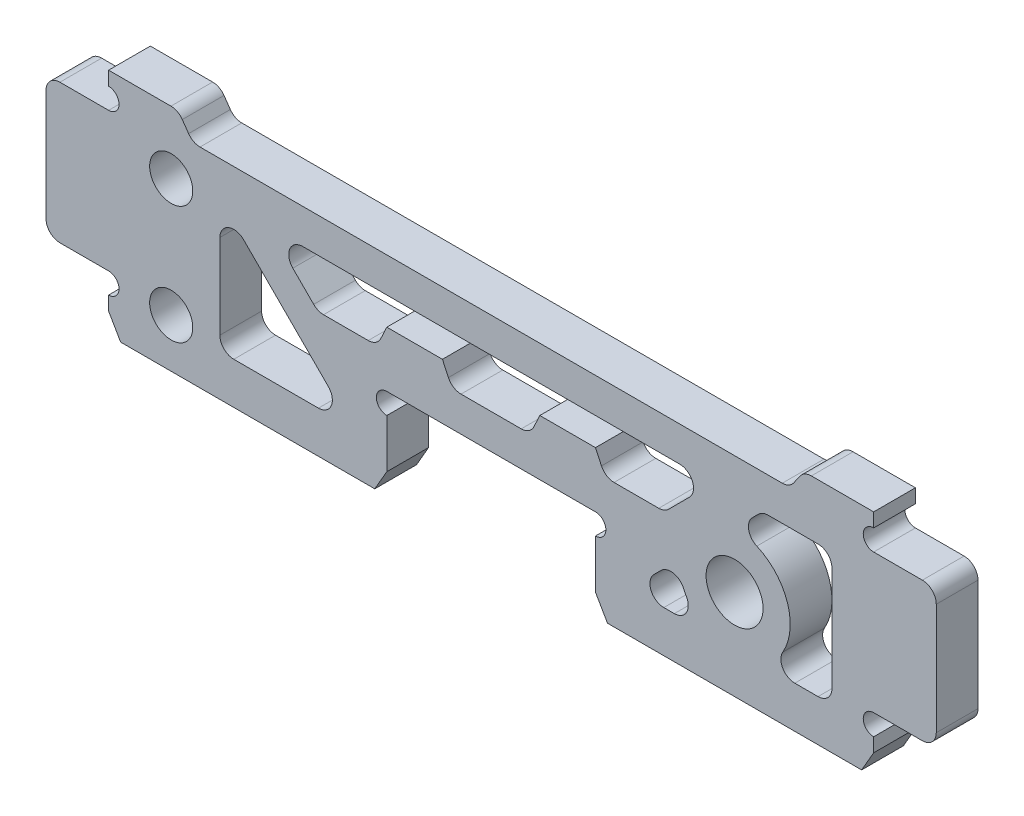
SolidWorks part; units mm, degrees
ref_plane "前视基准面" through (0, 0, 0) normal (0, 0, 1) x (1, 0, 0)
ref_plane "上视基准面" through (0, 0, 0) normal (0, 1, 0) x (1, 0, 0)
ref_plane "右视基准面" through (0, 0, 0) normal (1, 0, 0) x (0, 0, -1)
sketch "草图1" plane through (0, 0, 0) normal (0, 0, 1) x (1, 0, 0)
  line L0 (10, 10) -> (10, -5)
  line L1 (10, -5) -> (-10, -5)
  line L2 (-10, -5) -> (-10, 0)
  line L3 (-10, 0) -> (-25, 0)
  line L4 (-25, 0) -> (-25, -5)
  line L5 (-25, -5) -> (-45, -5)
  line L6 (-45, -5) -> (-45, 10)
  line L7 (-45, 10) -> (10, 10)
  circle A0 centre (0, 0) radius 2.05
  dimension "D1" = 10
  dimension "D2" = 4.1
  dimension "D3" = 5
  dimension "D4" = 5
  dimension "D5" = 20
  dimension "D6" = 15
  dimension "D7" = 55
  dimension "D8" = 15
extrude "凸台-拉伸1" add sketch "草图1" along normal mid plane 3
sketch "草图2" plane through (0, 0, 1.5) normal (0, 0, 1) x (1, 0, 0)
  line L0 (10, -2.5) -> (14.5, -2.5)
  line L1 (10, -5) -> (10, 10) construction
  line L2 (14.5, -2.5) -> (14.5, 7.5)
  line L3 (14.5, 7.5) -> (10, 7.5)
  line L4 (10, 7.5) -> (10, -2.5)
  line L5 (-45, 7.5) -> (-49.5, 7.5)
  line L6 (-45, 10) -> (-45, -5) construction
  line L7 (-49.5, 7.5) -> (-49.5, -2.5)
  line L8 (-49.5, -2.5) -> (-45, -2.5)
  line L9 (-45, -2.5) -> (-45, 7.5)
  line L10 (10, 10) -> (-45, 10) construction
  point P5 (10, 2.5)
  dimension "D1" = 10
  dimension "D2" = 4.5
  dimension "D3" = 4.5
  dimension "D4" = 2.5
extrude "凸台-拉伸2" add sketch "草图2" against normal up to surface (3 mm away) up to face at (-17.5, 0, -1.5)
sketch "草图3" plane through (0, 0, 1.5) normal (0, 0, 1) x (1, 0, 0)
  line L0 (-45, 10) -> (-45, 7.5) construction
  line L1 (-45, -2.5) -> (-45, -5) construction
  line L3 (10, -5) -> (10, -2.5) construction
  line L4 (10, 7.5) -> (10, 10) construction
  line L5 (-25, -5) -> (-25, 0) construction
  line L6 (-10, 0) -> (-10, -5) construction
  circle A0 centre (-45, 8.25) radius 0.75
  circle A1 centre (-45, -3.25) radius 0.75
  circle A2 centre (10, 8.25) radius 0.75
  circle A3 centre (10, -3.25) radius 0.75
  circle A4 centre (-25, -0.75) radius 0.75
  circle A5 centre (-10, -0.75) radius 0.75
  dimension "D1" = 1.5
extrude "切除-拉伸1" cut sketch "草图3" against normal through all
fillet "圆角1" radius 1 4 edges at (14.5, -2.5, 0) (14.5, 7.5, 0) (-49.5, 7.5, 0) (-49.5, -2.5, 0)
sketch "草图4" plane through (0, 0, 1.5) normal (0, 0, 1) x (1, 0, 0)
  line L0 (-10, -5) -> (-9.134, -6.5)
  line L1 (-9.134, -6.5) -> (9.134, -6.5)
  line L2 (9.134, -6.5) -> (10, -5)
  line L3 (-10, -5) -> (10, -5)
  dimension "D1" = 60
  dimension "D2" = 1.5
extrude "凸台-拉伸3" add sketch "草图4" against normal up to surface (3 mm away) up to face at (-17.5, 1.4231, -1.5)
ref_plane "基准面1" through (-17.5, 0, 0) normal (1, 0, 0) x (0, 0, -1)
mirror "镜向1" about plane through (-17.5, 0, 0) normal (1, 0, 0) of "凸台-拉伸3"
sketch "草图5" plane through (0, 0, 1.5) normal (0, 0, 1) x (1, 0, 0)
  line L0 (-40, 10) -> (-38.9497, 8.5)
  line L1 (10, 10) -> (-45, 10) construction
  line L2 (-38.9497, 8.5) -> (3.9497, 8.5)
  line L3 (3.9497, 8.5) -> (5, 10)
  line L4 (5, 10) -> (-40, 10)
  line L5 (-45, 10) -> (-45, 9) construction
  point P4 (-17.5, 10)
  dimension "D1" = 1.5
  dimension "D2" = 55
  dimension "D3" = 5
extrude "切除-拉伸2" cut sketch "草图5" against normal through all
fillet "圆角2" radius 1 4 edges at (5, 10, 0) (3.9497, 8.5, 0) (-40, 10, 0) (-38.9497, 8.5, 0)
sketch "草图6" plane through (0, 0, 1.5) normal (0, 0, 1) x (1, 0, 0)
  line L0 (-38.4291, 8.5) -> (3.4291, 8.5) construction
  line L1 (-45, 10) -> (-45, 9) construction
  line L2 (-25.866, -6.5) -> (-44.134, -6.5) construction
  circle A0 centre (-40.5, 5.5) radius 1.55
  circle A1 centre (-40.5, -3) radius 1.55
  dimension "D1" = 3
  dimension "D2" = 4.5
  dimension "D3" = 3.1
  dimension "D4" = 3.5
extrude "切除-拉伸3" cut sketch "草图6" against normal through all
sketch "草图7" plane through (0, 0, 1.5) normal (0, 0, 1) x (1, 0, 0)
  line L0 (-37, 6) -> (-37, -3.5)
  line L1 (-37, -3.5) -> (-27.5, -3.5)
  line L2 (-27.5, -3.5) -> (-37, 6)
  line L3 (-25.866, -6.5) -> (-44.134, -6.5) construction
  line L4 (-25, -5) -> (-25, -1.5) construction
  line L5 (-38.4291, 8.5) -> (3.4291, 8.5) construction
  line L6 (-33.4645, 6) -> (-1.5355, 6)
  line L7 (-1.5355, 6) -> (-5.0355, 2.5)
  line L8 (-5.0355, 2.5) -> (-29.9645, 2.5)
  line L9 (-29.9645, 2.5) -> (-33.4645, 6)
  line L11 (-25, 0) -> (-10, 0) construction
  circle A0 centre (-40.5, 5.5) radius 1.55 construction
  point P19 (-17.5, 0)
  point P20 (-17.5, 2.5)
  point P21 (-17.5, 6)
  dimension "D1" = 3
  dimension "D2" = 3.5
  dimension "D3" = 2.5
  dimension "D4" = 2.5
  dimension "D5" = 2.5
  dimension "D6" = 2.5
extrude "切除-拉伸4" cut sketch "草图7" against normal through all
fillet "圆角3" radius 1 7 edges at (-1.5355, 6, 0) (-5.0355, 2.5, 0) (-29.9645, 2.5, 0) (-33.4645, 6, 0) (-37, -3.5, 0) (-27.5, -3.5, 0) (-37, 6, 0)
sketch "草图8" plane through (0, 0, 1.5) normal (0, 0, 1) x (1, 0, 0)
  line L0 (7, 6) -> (7, -3.5)
  line L1 (7, -3.5) -> (1.9365, -3.5)
  line L2 (7, 6) -> (2, 6)
  line L3 (2, 6) -> (0, 4)
  line L4 (-3.9497, 6) -> (-31.0503, 6) construction
  line L5 (-4.7426, 2.7929) -> (-3.2426, 4.2929) construction
  line L6 (-36, -3.5) -> (-29.9142, -3.5) construction
  line L7 (-1.9365, -3.5) -> (-7.5, -3.5)
  line L8 (-7.5, -3.5) -> (-4, 0)
  arc A0 (1.9365, -3.5) -> (0, 4) centre (0, 0) ccw
  arc A1 (10, 9) -> (10, 7.5) centre (10, 8.25) ccw construction
  arc A2 (-4, 0) -> (-1.9365, -3.5) centre (0, 0) ccw
  dimension "D1" = 8
  dimension "D2" = 2.5
  dimension "D3" = 3
extrude "切除-拉伸5" cut sketch "草图8" against normal through all
fillet "圆角4" radius 1 8 edges at (0, 4, 0) (2, 6, 0) (7, 6, 0) (7, -3.5, 0) (1.9365, -3.5, 0) (-1.9365, -3.5, 0) (-4, 0, 0) (-7.5, -3.5, 0)
sketch "草图9" plane through (0, 0, 1.5) normal (0, 0, 1) x (1, 0, 0)
  line L0 (-25, 2.5) -> (-25, 4)
  line L1 (-29.5503, 2.5) -> (-5.4497, 2.5) construction
  line L2 (-25, 4) -> (-21, 4)
  line L3 (-21, 4) -> (-21, 2.5)
  line L4 (-21, 2.5) -> (-25, 2.5)
  line L5 (-14, 2.5) -> (-14, 4)
  line L6 (-14, 4) -> (-10, 4)
  line L7 (-10, 4) -> (-10, 2.5)
  line L8 (-10, -1.5) -> (-10, -5) construction
  line L9 (-14, 2.5) -> (-10, 2.5)
  line L10 (-25, -5) -> (-25, -1.5) construction
  dimension "D1" = 1.5
  dimension "D2" = 4
extrude "凸台-拉伸4" add sketch "草图9" against normal up to surface (3 mm away) up to face at (4.1595, 2.0321, -1.5)
chamfer "倒角1" distance 1.5 angle 25 4 edges at (-14, 2.5, 0) (-10, 2.5, 0) (-21, 2.5, 0) (-25, 2.5, 0)
fillet "圆角5" radius 1 4 edges at (-9.3005, 2.5, 0) (-14.6995, 2.5, 0) (-20.3005, 2.5, 0) (-25.6995, 2.5, 0)
